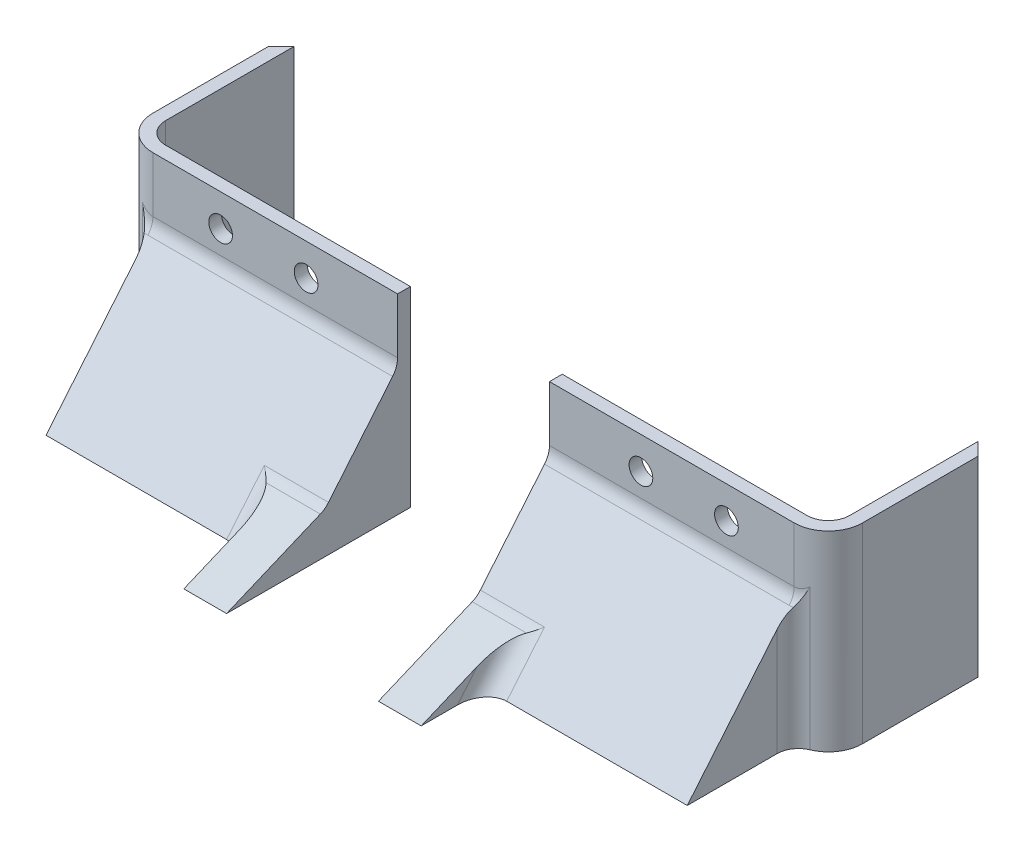
SolidWorks part; units mm, degrees
ref_plane "Front Plane" through (0, 0, 0) normal (0, 0, 1) x (1, 0, 0)
ref_plane "Top Plane" through (0, 0, 0) normal (0, 1, 0) x (1, 0, 0)
ref_plane "Right Plane" through (0, 0, 0) normal (1, 0, 0) x (0, 0, -1)
sketch "Sketch1" plane through (0, 0, 0) normal (0, 1, 0) x (1, 0, 0)
  line L21 (65.2354, 35) -> (65.2354, 8)
  line L22 (62.2354, 38) -> (65.2354, 35)
  line L23 (0, 0) -> (57.2354, 0)
  line L24 (0, 3) -> (57.2354, 3)
  line L25 (62.2354, 38) -> (62.2354, 8)
  line L26 (0, 3) -> (0, 0)
  arc A3 (57.2354, 0) -> (65.2354, 8) centre (57.2354, 8) ccw
  arc A4 (57.2354, 3) -> (62.2354, 8) centre (57.2354, 8) ccw
  dimension "D4" = 8
  dimension "D1" = 57.2354
  dimension "D2" = 3
  dimension "D3" = 3
  dimension "D5" = 27
extrude "Boss-Extrude1" add sketch "Sketch1" against normal blind 44.75 contours A3 L21 L22 L25 A4 L24 L26 L23
sketch "Sketch3" plane through (0, 0, 0) normal (-1, 0, 0) x (0, 0, 1)
  line L0 (0, -44.75) -> (25, -44.75)
  line L2 (0, -44.75) -> (0, 0) construction
  line L3 (0, -14.75) -> (25, -44.75)
  line L4 (25, -44.75) -> (40, -44.75)
  line L5 (40, -44.75) -> (16.9445, -35.0834)
  line L6 (16.9445, -35.0834) -> (25, -44.75)
  line L7 (0, -44.75) -> (0, -14.75)
  line L8 (-3, -44.75) -> (0, -44.75) construction
  dimension "D1" = 25
  dimension "D2" = 30
  dimension "D3" = 15
  dimension "D4" = 25
extrude "Boss-Extrude2" add sketch "Sketch3" against normal up to vertex (57.2354 mm away) contours L0 L7 L3 region at (0, -34.75, 8.3333) up to point (57.2354, -44.75, 0)
sketch "Sketch4" plane through (0, 0, 0) normal (-1, 0, 0) x (0, 0, 1)
  line L0 (25, -44.75) -> (40, -44.75)
  line L1 (40, -44.75) -> (16.9445, -35.0834)
  line L2 (0, -14.75) -> (25, -44.75) construction
  line L3 (16.9445, -35.0834) -> (25, -44.75)
  dimension "D1" = 15
  dimension "D2" = 25
extrude "Boss-Extrude6" add sketch "Sketch4" against normal blind 10
sketch "Sketch6" plane through (0, 0, -3) normal (0, 0, -1) x (-1, 0, 0)
  line L0 (-57.514, 0) -> (-41.394, 0) construction
  line L1 (55, 0) -> (-55, 0) construction
  line L2 (-41.394, 0) -> (-41.394, -7.5) construction
  circle A0 centre (-41.394, -7.5) radius 2.775
  circle A1 centre (-21.394, -7.5) radius 2.775
  dimension "D3" = 5.55
  dimension "D1" = 16.12
  dimension "D2" = 7.5
extrude "Cut-Extrude1" cut sketch "Sketch6" against normal up to surface (3 mm away) up to face at (28.6177, -7.375, 0)
ref_plane "Plane1" through (-17.76, 0, 0) normal (1, 0, 0) x (0, 0, -1)
fillet "Fillet4" radius 5 4 edges at (57.2354, -29.75, 0) (28.6177, -14.75, 0) (10, -39.9167, 20.9722) (5, -35.0834, 16.9445)
mirror "Mirror17" about plane through (-17.76, 0, 0) normal (1, 0, 0) of bodies 118
